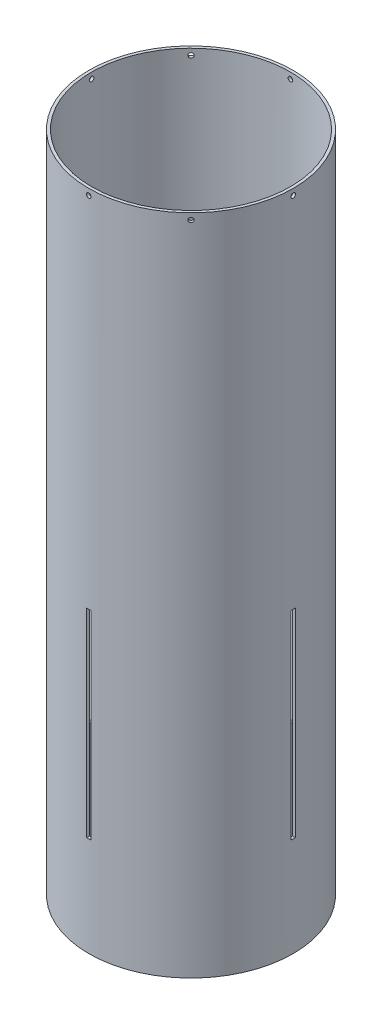
SolidWorks part; units mm, degrees
ref_plane "Front Plane" through (0, 0, 0) normal (0, 0, 1) x (1, 0, 0)
ref_plane "Top Plane" through (0, 0, 0) normal (0, 1, 0) x (1, 0, 0)
ref_plane "Right Plane" through (0, 0, 0) normal (1, 0, 0) x (0, 0, -1)
sketch "Sketch1" plane through (0, 0, 0) normal (0, 1, 0) x (1, 0, 0)
  circle A0 centre (0, 0) radius 76.2
  circle A1 centre (0, 0) radius 78.359
  dimension "D1" = 152.4
  dimension "D2" = 156.718
extrude "Boss-Extrude1" add sketch "Sketch1" along normal blind 508
ref_axis "Axis1" through (0, 508, 0) along (0, -1, 0)
sketch "Sketch2" plane through (0, 0, 0) normal (1, 0, 0) x (0, 0, -1)
  line L0 (0, 0) -> (0, 76.2)
  line L1 (1.5875, 76.2) -> (-1.5875, 76.2)
  line L2 (1.5875, 76.2) -> (1.5875, 228.6)
  line L3 (1.5875, 228.6) -> (-1.5875, 228.6)
  line L4 (-1.5875, 76.2) -> (-1.5875, 228.6)
  line L5 (1.5875, 76.2) -> (-1.5875, 228.6) construction
  line L6 (1.5875, 228.6) -> (-1.5875, 76.2) construction
  line L7 (78.359, 508) -> (-78.359, 508) construction
  line L8 (78.359, 508) -> (-78.359, 508)
  line L9 (0, 508) -> (0, 503.2375)
  circle A0 centre (0, 503.2375) radius 1.75
  point P0 (0, 152.4)
  dimension "D4" = 3.5
  dimension "D1" = 3.175
  dimension "D2" = 152.4
  dimension "D3" = 76.2
  dimension "D5" = 4.7625
extrude "Cut-Extrude1" cut sketch "Sketch2" against normal through all contours L4 L1 L2 L3 region at (0, 152.4, 0)
pattern_circular "CirPattern1" count 4 over 360 about axis through (0, 0, 0) along (0, 1, 0) of "Cut-Extrude1" reverse direction yes
extrude "Cut-Extrude2" cut sketch "Sketch2<3>" against normal through all contours A0 region at (0, 502.0351, 1.2024)
sketch "Sketch2<3>" plane through (0, 0, 0) normal (1, 0, 0) x (0, 0, -1) same geometry as "Sketch2"
pattern_circular "CirPattern2" count 8 over 360 about axis through (0, 508, 0) along (0, -1, 0) of "Cut-Extrude2"
equation "\"Aft_Lower_Length\"= 20in"
equation "\"D1@Boss-Extrude1\"=\"Aft_Lower_Length\""
equation "\"AB_Coupler_OD_Length\"= 2in"
equation "\"AB_Coupling_Section_Length\"= 0.375in"
equation "\"AB_Coupler_Length\"= \"AB_Coupler_OD_Length\" + \"AB_Coupling_Section_Length\" * 2"
equation "\"AB_Coupler_Num_Screws\"= 8"
equation "\"AB_Coupling_Screw_Diameter\"= 3.5mm"
equation "\"Aft_Upper_Length\"= \"Aft_Section_Length\" - \"Aft_Lower_Length\" - \"AB_Coupler_OD_Length\""
equation "\"Aft_Section_Length\"= 40in"
equation "\"D4@Sketch2\"=\"AB_Coupling_Screw_Diameter\""
equation "\"D5@Sketch2\"=\"AB_Coupling_Section_Length\"/2"
equation "\"D1@CirPattern2\"=\"AB_Coupler_Num_Screws\""
